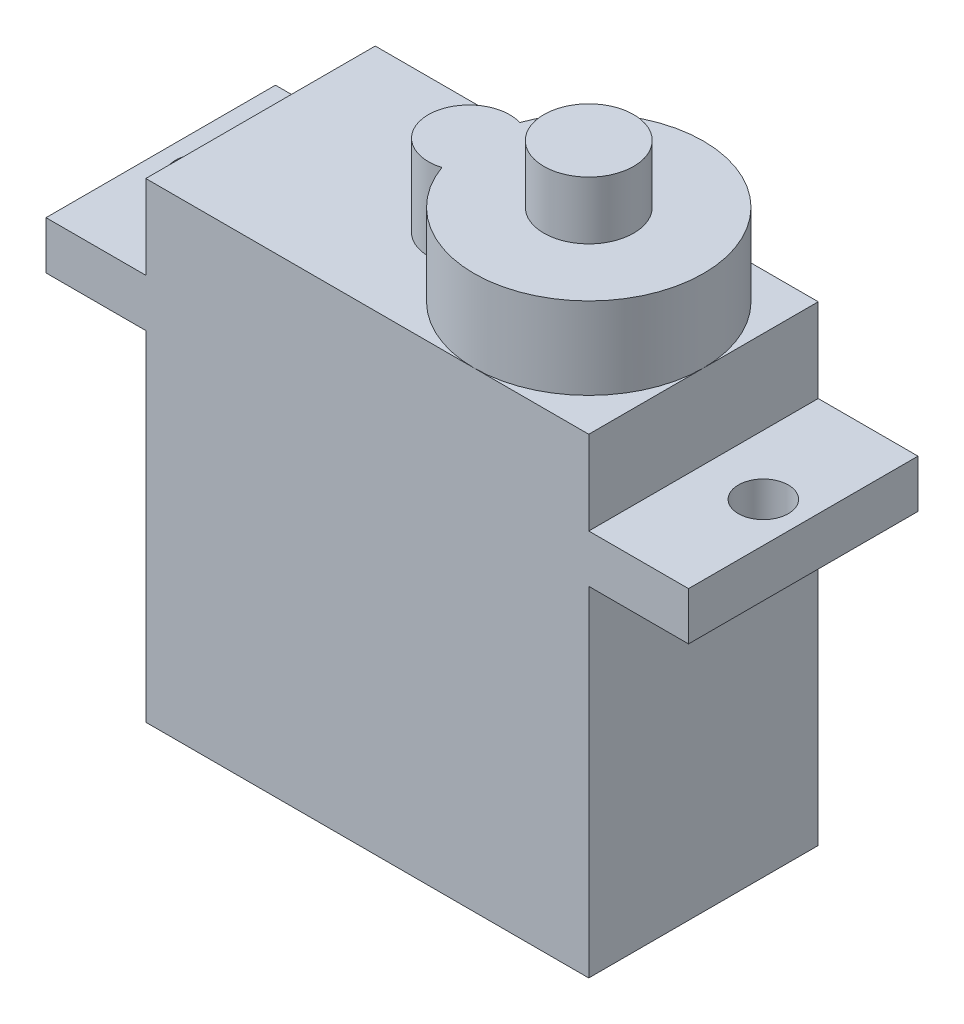
SolidWorks part; units mm, degrees
ref_plane "Front Plane" through (0, 0, 0) normal (0, 0, 1) x (1, 0, 0)
ref_plane "Top Plane" through (0, 0, 0) normal (0, 1, 0) x (1, 0, 0)
ref_plane "Right Plane" through (0, 0, 0) normal (1, 0, 0) x (0, 0, -1)
sketch "Sketch2" plane through (0, 0, 0) normal (0, 0, 1) x (1, 0, 0)
  line L1 (-11.1, 11.8) -> (11.1, 11.8)
  line L2 (-11.1, 11.8) -> (-11.1, -11.8)
  line L3 (-11.1, -11.8) -> (11.1, -11.8)
  line L4 (11.1, 11.8) -> (11.1, -11.8)
  line L5 (-11.1, 11.8) -> (11.1, -11.8) construction
  line L6 (-11.1, -11.8) -> (11.1, 11.8) construction
  point P0 (0, 0)
  dimension "D1" = 23.6
  dimension "D2" = 22.2
extrude "Boss-Extrude1" add sketch "Sketch2" along normal blind 11.5
sketch "Sketch4" plane through (11.1, 0, 0) normal (1, 0, 0) x (0, 0, -1)
  line L1 (-11.5, 5.2) -> (0, 5.2)
  line L2 (-11.5, -11.8) -> (-11.5, 11.8) construction
  line L3 (0, -11.8) -> (0, 11.8) construction
  line L4 (-11.5, -11.8) -> (0, -11.8) construction
  line L5 (-11.5, 7.6) -> (0, 7.6)
  line L6 (-11.5, 7.6) -> (-11.5, 5.2)
  line L7 (0, 7.6) -> (0, 5.2)
  dimension "D1" = 17
  dimension "D2" = 2.4
extrude "Boss-Extrude3" add sketch "Sketch4" along normal blind 5
mirror "Mirror1" about plane through (0, 0, 0) normal (1, 0, 0) of "Boss-Extrude3"
sketch "Sketch5" plane through (0, 7.6, 0) normal (0, 1, 0) x (1, 0, 0)
  line L0 (16.1, -5.75) -> (-16.1, -5.75) construction
  line L1 (16.1, 0) -> (16.1, -11.5) construction
  line L2 (-16.1, 0) -> (-16.1, -11.5) construction
  line L3 (0, 0) -> (0, -11.5) construction
  line L4 (11.1, -11.5) -> (-11.1, -11.5) construction
  circle A0 centre (14.1, -5.75) radius 1.25
  circle A1 centre (-14.1, -5.75) radius 1.25
  dimension "D2" = 2.5
  dimension "D1" = 2
extrude "Cut-Extrude1" cut sketch "Sketch5" against normal blind 5
sketch "Sketch7" plane through (0, 11.8, 0) normal (0, 1, 0) x (1, 0, 0)
  line L0 (11.1, 0) -> (11.1, -11.5) construction
  line L2 (11.1, 0) -> (-11.1, 0) construction
  line L3 (11.1, -11.5) -> (-11.1, -11.5) construction
  arc A0 (-0.0587, -7.7016) -> (-0.0587, -3.7984) centre (5.35, -5.75) ccw
  circle A1 centre (5.35, -5.75) radius 2.25
  arc A2 (-0.0587, -3.7984) -> (-0.0587, -7.7016) centre (-0.65, -5.75) ccw
  dimension "D1" = 4.5
  dimension "2.5" = 2.0392
  dimension "D2" = 6
extrude "Boss-Extrude4" add sketch "Sketch7" along normal blind 4.1 contours A0 A2 A1 region at (-2.5097, 11.8, 5.75)
extrude "Boss-Extrude5" add sketch "Sketch7<3>" along normal blind 7 separate body contours A1 region at (5.35, 11.8, 5.75)
sketch "Sketch7<3>" plane through (0, 11.8, 0) normal (0, 1, 0) x (1, 0, 0) same geometry as "Sketch7"
sketch "Sketch8" plane through (0, 7.6, 0) normal (0, 1, 0) x (1, 0, 0)
  line L0 (11.1, -5.75) -> (11.1, 0) construction
  line L1 (11.1, -11.5) -> (5.35, -11.5) construction
  line L2 (5.35, -11.5) -> (-11.1, -11.5) construction
  line L3 (11.1, 0) -> (11.1, -11.5) construction
  line L4 (11.1, -11.5) -> (11.1, -5.75) construction
  line L5 (16.1, -11.5) -> (11.1, -11.5) construction
  line L6 (16.1, 0) -> (16.1, -11.5) construction
  line L7 (16.1, 0) -> (11.1, 0) construction
  line L8 (11.1, 0) -> (5.35, 0) construction
  line L9 (5.35, 0) -> (-11.1, 0) construction
  line L10 (-11.1, -11.5) -> (-11.1, 0) construction
  line L11 (-16.1, -11.5) -> (-11.1, -11.5) construction
  line L12 (-16.1, 0) -> (-11.1, 0) construction
  line L13 (-16.1, 0) -> (-16.1, -11.5) construction
  line L14 (11.1, -5.75) -> (11.1, 0)
  line L15 (11.1, -11.5) -> (5.35, -11.5)
  line L16 (5.35, -11.5) -> (-11.1, -11.5)
  line L17 (11.1, 0) -> (11.1, -11.5)
  line L18 (11.1, -11.5) -> (11.1, -5.75)
  line L19 (16.1, -11.5) -> (11.1, -11.5)
  line L20 (16.1, 0) -> (16.1, -11.5)
  line L21 (16.1, 0) -> (11.1, 0)
  line L22 (11.1, 0) -> (5.35, 0)
  line L23 (5.35, 0) -> (-11.1, 0)
  line L24 (-11.1, -11.5) -> (-11.1, 0)
  line L25 (-16.1, -11.5) -> (-11.1, -11.5)
  line L26 (-16.1, 0) -> (-11.1, 0)
  line L27 (-16.1, 0) -> (-16.1, -11.5)
  arc A0 (-0.0587, -3.7984) -> (-0.0587, -7.7016) centre (-0.65, -5.75) ccw construction
  circle A1 centre (5.35, -5.75) radius 2.25 construction
  arc A2 (-0.0587, -3.7984) -> (-0.0587, -7.7016) centre (-0.65, -5.75) ccw construction
  arc A3 (-0.0587, -7.7016) -> (-0.0587, -3.7984) centre (5.35, -5.75) ccw construction
  arc A4 (11.1, -5.75) -> (5.35, 0) centre (5.35, -5.75) ccw construction
  circle A5 centre (14.1, -5.75) radius 1.25 construction
  circle A6 centre (-14.1, -5.75) radius 1.25 construction
  arc A7 (-0.0587, -3.7984) -> (-0.0587, -7.7016) centre (-0.65, -5.75) ccw
  circle A8 centre (5.35, -5.75) radius 2.25
  arc A9 (-0.0587, -3.7984) -> (-0.0587, -7.7016) centre (-0.65, -5.75) ccw
  arc A10 (-0.0587, -7.7016) -> (-0.0587, -3.7984) centre (5.35, -5.75) ccw
  arc A11 (11.1, -5.75) -> (5.35, 0) centre (5.35, -5.75) ccw
  circle A12 centre (14.1, -5.75) radius 1.25
  circle A13 centre (-14.1, -5.75) radius 1.25
